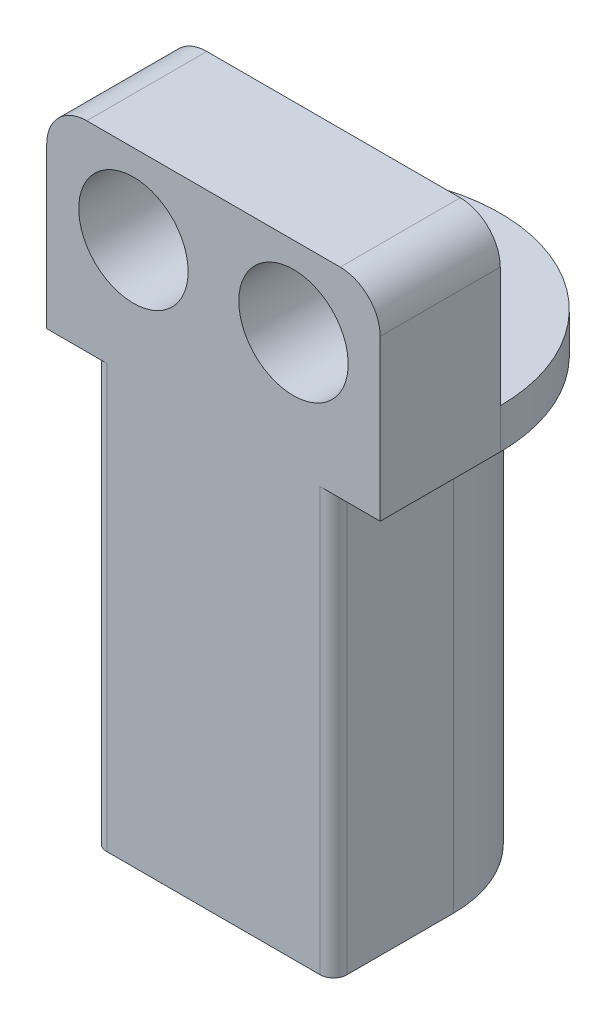
SolidWorks part; units mm, degrees
ref_plane "正面" through (0, 0, 0) normal (0, 0, 1) x (1, 0, 0)
ref_plane "平面" through (0, 0, 0) normal (0, 1, 0) x (1, 0, 0)
ref_plane "右側面" through (0, 0, 0) normal (1, 0, 0) x (0, 0, -1)
sketch "ｽｹｯﾁ1" plane through (0, 0, 0) normal (0, 1, 0) x (1, 0, 0)
  line L0 (-9, 0) -> (-9, -9)
  line L1 (-9, -9) -> (9, -9)
  line L2 (9, -9) -> (9, 0)
  arc A0 (9, 0) -> (-9, 0) centre (0, 0) ccw
  circle A1 centre (0, 0) radius 7.6
  dimension "D1" = 15.2
  dimension "D2" = 18
extrude "ﾎﾞｽ - 押し出し1" add sketch "ｽｹｯﾁ1" along normal blind 5
sketch "ｽｹｯﾁ2" plane through (0, 5, 0) normal (0, 1, 0) x (1, 0, 0)
  line L0 (9, -9) -> (9, 0) construction
  line L1 (-9, -9) -> (9, -9)
  line L2 (-9, -9) -> (-9, -4)
  line L3 (-9, -4) -> (9, -4)
  line L4 (9, -9) -> (9, -4)
  dimension "D1" = 5
extrude "ﾎﾞｽ - 押し出し2" add sketch "ｽｹｯﾁ2" along normal blind 15
sketch "ｽｹｯﾁ4" plane through (0, 5, 0) normal (0, 1, 0) x (1, 0, 0)
  line L2 (-12.5, 0) -> (-12.5, -9)
  line L3 (-12.5, -9) -> (12.5, -9)
  line L4 (12.5, -9) -> (12.5, 0)
  line L5 (-9, -9) -> (9, -9) construction
  arc A0 (12.5, 0) -> (-12.5, 0) centre (0, 0) ccw
  dimension "D1" = 25
extrude "ﾎﾞｽ - 押し出し3" add sketch "ｽｹｯﾁ4" along normal blind 3
sketch "ｽｹｯﾁ5" plane through (0, 8, 0) normal (0, 1, 0) x (1, 0, 0)
  line L1 (-9, -4) -> (-12.5, -4)
  line L2 (-9, -4) -> (-9, -9)
  line L3 (-9, -9) -> (-12.5, -9)
  line L4 (-12.5, -4) -> (-12.5, -9)
  line L5 (9, -4) -> (12.5, -4)
  line L6 (9, -4) -> (9, -9)
  line L7 (9, -9) -> (12.5, -9)
  line L8 (12.5, -4) -> (12.5, -9)
extrude "ﾎﾞｽ - 押し出し4" add sketch "ｽｹｯﾁ5" along normal up to surface (12 mm away) up to face at (0, 20, 6.5)
sketch "ｽｹｯﾁ3" plane through (0, 0, 9) normal (0, 0, 1) x (1, 0, 0)
  line L0 (-9, 14) -> (9, 14) construction
  line L3 (0, 20) -> (0, 5) construction
  line L4 (-12.5, 20) -> (12.5, 20) construction
  line L5 (-9, 5) -> (9, 5) construction
  line L6 (-9, 5) -> (-9, 0) construction
  line L7 (9, 5) -> (9, 0) construction
  line L8 (-12.5, 20) -> (12.5, 20) construction
  circle A0 centre (-6, 14) radius 4.1
  circle A1 centre (6, 14) radius 4.1
  dimension "D1" = 8.2
  dimension "D2" = 12
  dimension "D3" = 6
extrude "ｶｯﾄ - 押し出し1" cut sketch "ｽｹｯﾁ3" against normal through all
fillet "ﾌｨﾚｯﾄ4" radius 1 2 edges at (-9, 2.5, 9) (9, 2.5, 9)
sketch "ｽｹｯﾁ6" plane through (0, 0, 4) normal (0, 0, -1) x (-1, 0, 0)
  line L4 (12.5, 20) -> (-12.5, 20)
  line L5 (-12.5, 20) -> (-12.5, 8)
  line L6 (-12.5, 8) -> (12.5, 8)
  line L7 (12.5, 8) -> (12.5, 20)
  line L8 (12.5, 20) -> (-12.5, 20)
  line L9 (-12.5, 20) -> (-12.5, 8)
  line L10 (-12.5, 8) -> (12.5, 8)
  line L11 (12.5, 8) -> (12.5, 20)
  circle A1 centre (-6, 14) radius 4.1
  circle A2 centre (-6, 14) radius 4.1
  circle A3 centre (6, 14) radius 4.1
  circle A4 centre (6, 14) radius 4.1
  dimension "D1" = 0
  dimension "D2" = 0
  dimension "D3" = 0
extrude "ﾎﾞｽ - 押し出し5" add sketch "ｽｹｯﾁ6" along normal up to vertex (4 mm away)
fillet "ﾌｨﾚｯﾄ5" radius 3 2 edges at (12.5, 20, 4.5) (-12.5, 20, 4.5)
sketch "ｽｹｯﾁ7" plane through (0, 0, 0) normal (0, -1, 0) x (1, 0, 0)
  line L3 (8, 9) -> (-8, 9)
  line L4 (-9, 8) -> (-9, 0)
  line L5 (9, 0) -> (9, 8)
  line L6 (8, 9) -> (-8, 9)
  line L7 (-9, 8) -> (-9, 0)
  line L8 (9, 0) -> (9, 8)
  circle A0 centre (0, 0) radius 8.4
  arc A4 (-8, 9) -> (-9, 8) centre (-8, 8) ccw
  arc A5 (-9, 0) -> (9, 0) centre (0, 0) ccw
  arc A6 (9, 8) -> (8, 9) centre (8, 8) ccw
  arc A7 (-8, 9) -> (-9, 8) centre (-8, 8) ccw
  arc A8 (-9, 0) -> (9, 0) centre (0, 0) ccw
  arc A9 (9, 8) -> (8, 9) centre (8, 8) ccw
  dimension "D1" = 16.8
  dimension "D2" = 0
extrude "ﾎﾞｽ - 押し出し6" add sketch "ｽｹｯﾁ7" along normal blind 26.7
sketch "ｽｹｯﾁ9" plane through (0, 5, 0) normal (0, -1, 0) x (1, 0, 0)
  circle A0 centre (0, 0) radius 8.4
  circle A1 centre (0, 0) radius 8.4 construction
extrude "ﾎﾞｽ - 押し出し8" add sketch "ｽｹｯﾁ9" along normal up to surface (31.7 mm away) up to face at (0, -26.7, 4.2357)
sketch "ｽｹｯﾁ10" plane through (0, -26.7, 0) normal (0, -1, 0) x (1, 0, 0)
  circle A0 centre (0, 0) radius 2.05
  dimension "D1" = 4.1
extrude "ｶｯﾄ - 押し出し2" cut sketch "ｽｹｯﾁ10" against normal blind 5
